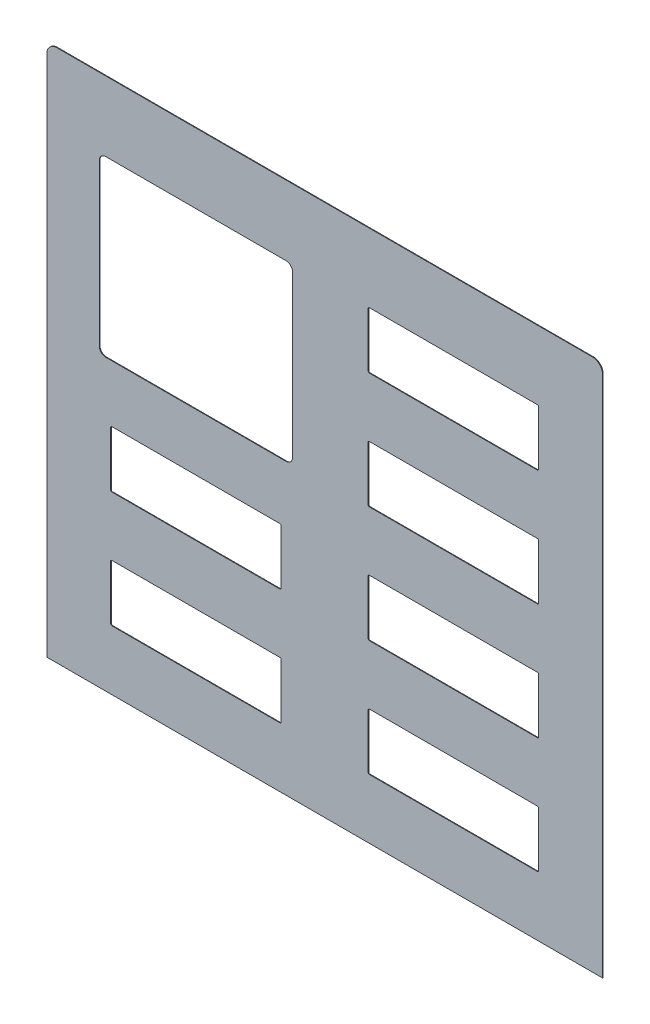
SolidWorks part; units mm, degrees
ref_plane "Front Plane" through (0, 0, 0) normal (0, 0, 1) x (1, 0, 0)
ref_plane "Top Plane" through (0, 0, 0) normal (0, 1, 0) x (1, 0, 0)
ref_plane "Right Plane" through (0, 0, 0) normal (1, 0, 0) x (0, 0, -1)
sketch "Sketch1" plane through (0, 0, 0) normal (0, 0, 1) x (1, 0, 0)
  line L1 (0, 0) -> (863.4, 0)
  line L2 (0, 0) -> (0, 812)
  line L3 (15.7, 827.7) -> (847.7, 827.7)
  line L4 (863.4, 0) -> (863.4, 812)
  arc A0 (847.7, 827.7) -> (863.4, 812) centre (847.7, 812) cw
  arc A1 (0, 812) -> (15.7, 827.7) centre (15.7, 812) cw
  dimension "D3" = 15.7
  dimension "D1" = 863.4
  dimension "D2" = 827.7
base flange "Base-Flange1" sketch "Sketch1" thickness 1 reverse thickness direction no parameters "D1"=1
edge flange "Edge-Flange1" [suppressed] sketch "Sketch8" flange angle 90 flange position material inside bend radius 1 thickness 1
sketch "Sketch8" plane through (0, 0, -1) normal (0, -1, 0) x (-1, 0, 0)
  line L0 (0, 0) -> (-822, 0) construction
  line L1 (-42, 0) -> (-780, 0)
  line L2 (-780, 0) -> (-780, 12)
  line L3 (-780, 12) -> (-42, 12)
  line L4 (-42, 12) -> (-42, 0)
  line L5 (0, 0) -> (0, -1) construction
  line L6 (-822, 0) -> (-822, -1) construction
  circle A0 centre (-81, 6) radius 2.75
  circle A1 centre (-261, 6) radius 2.75
  circle A2 centre (-441, 6) radius 2.75
  circle A3 centre (-621, 6) radius 2.75
  circle A4 centre (-801, 6) radius 2.75
  circle A5 centre (-981, 6) radius 2.75
  circle A6 centre (-1161, 6) radius 2.75
  point P6 (-42, 6)
  dimension "D1" = 5.5
  dimension "D2" = 39
  dimension "D4" = 42
  dimension "D5" = 42
  dimension "D3" = 7
bend "EdgeBend1" bend radius 1 bend angle 90 parameters "D5"=1, "D6"=10, "D7"=12
sketch "Sketch9" plane through (0, 0, 0) normal (0, 0, 1) x (1, 0, 0)
  line L0 (863.4, 0) -> (863.4, 812) construction
  line L1 (762.2, 720.7) -> (501.2, 720.7)
  line L2 (764.2, 718.7) -> (764.2, 634.7)
  line L3 (762.2, 632.7) -> (501.2, 632.7)
  line L4 (499.2, 718.7) -> (499.2, 634.7)
  line L5 (847.7, 827.7) -> (15.7, 827.7) construction
  line L38 (764.2, 538.7) -> (764.2, 454.7)
  line L39 (762.2, 540.7) -> (501.2, 540.7)
  line L40 (762.2, 452.7) -> (501.2, 452.7)
  line L41 (499.2, 538.7) -> (499.2, 454.7)
  line L42 (764.2, 358.7) -> (764.2, 274.7)
  line L43 (762.2, 360.7) -> (501.2, 360.7)
  line L44 (762.2, 272.7) -> (501.2, 272.7)
  line L45 (499.2, 358.7) -> (499.2, 274.7)
  line L46 (764.2, 178.7) -> (764.2, 94.7)
  line L47 (762.2, 180.7) -> (501.2, 180.7)
  line L48 (762.2, 92.7) -> (501.2, 92.7)
  line L49 (499.2, 178.7) -> (499.2, 94.7)
  line L58 (364.2, 358.7) -> (364.2, 274.7)
  line L59 (362.2, 360.7) -> (101.2, 360.7)
  line L60 (362.2, 272.7) -> (101.2, 272.7)
  line L61 (99.2, 358.7) -> (99.2, 274.7)
  line L62 (364.2, 178.7) -> (364.2, 94.7)
  line L63 (362.2, 180.7) -> (101.2, 180.7)
  line L64 (362.2, 92.7) -> (101.2, 92.7)
  line L65 (99.2, 178.7) -> (99.2, 94.7)
  line L66 (364.2, 718.7) -> (364.2, 634.7) [skipped]
  line L67 (362.2, 720.7) -> (101.2, 720.7) [skipped]
  line L68 (362.2, 632.7) -> (101.2, 632.7) [skipped]
  line L69 (99.2, 718.7) -> (99.2, 634.7) [skipped]
  line L70 (364.2, 538.7) -> (364.2, 454.7) [skipped]
  line L71 (362.2, 540.7) -> (101.2, 540.7) [skipped]
  line L72 (362.2, 452.7) -> (101.2, 452.7) [skipped]
  line L73 (99.2, 538.7) -> (99.2, 454.7) [skipped]
  arc A0 (764.2, 634.7) -> (762.2, 632.7) centre (762.2, 634.7) cw
  arc A1 (501.2, 632.7) -> (499.2, 634.7) centre (501.2, 634.7) cw
  arc A2 (501.2, 720.7) -> (499.2, 718.7) centre (501.2, 718.7) ccw
  arc A3 (762.2, 720.7) -> (764.2, 718.7) centre (762.2, 718.7) cw
  arc A36 (762.2, 540.7) -> (764.2, 538.7) centre (762.2, 538.7) cw
  arc A37 (764.2, 454.7) -> (762.2, 452.7) centre (762.2, 454.7) cw
  arc A38 (501.2, 452.7) -> (499.2, 454.7) centre (501.2, 454.7) cw
  arc A39 (501.2, 540.7) -> (499.2, 538.7) centre (501.2, 538.7) ccw
  arc A40 (762.2, 360.7) -> (764.2, 358.7) centre (762.2, 358.7) cw
  arc A41 (764.2, 274.7) -> (762.2, 272.7) centre (762.2, 274.7) cw
  arc A42 (501.2, 272.7) -> (499.2, 274.7) centre (501.2, 274.7) cw
  arc A43 (501.2, 360.7) -> (499.2, 358.7) centre (501.2, 358.7) ccw
  arc A44 (762.2, 180.7) -> (764.2, 178.7) centre (762.2, 178.7) cw
  arc A45 (764.2, 94.7) -> (762.2, 92.7) centre (762.2, 94.7) cw
  arc A46 (501.2, 92.7) -> (499.2, 94.7) centre (501.2, 94.7) cw
  arc A47 (501.2, 180.7) -> (499.2, 178.7) centre (501.2, 178.7) ccw
  arc A56 (362.2, 360.7) -> (364.2, 358.7) centre (362.2, 358.7) cw
  arc A57 (364.2, 274.7) -> (362.2, 272.7) centre (362.2, 274.7) cw
  arc A58 (101.2, 272.7) -> (99.2, 274.7) centre (101.2, 274.7) cw
  arc A59 (101.2, 360.7) -> (99.2, 358.7) centre (101.2, 358.7) ccw
  arc A60 (362.2, 180.7) -> (364.2, 178.7) centre (362.2, 178.7) cw
  arc A61 (364.2, 94.7) -> (362.2, 92.7) centre (362.2, 94.7) cw
  arc A62 (101.2, 92.7) -> (99.2, 94.7) centre (101.2, 94.7) cw
  arc A63 (101.2, 180.7) -> (99.2, 178.7) centre (101.2, 178.7) ccw
  arc A64 (362.2, 720.7) -> (364.2, 718.7) centre (362.2, 718.7) cw [skipped]
  arc A65 (364.2, 634.7) -> (362.2, 632.7) centre (362.2, 634.7) cw [skipped]
  arc A66 (101.2, 632.7) -> (99.2, 634.7) centre (101.2, 634.7) cw [skipped]
  arc A67 (101.2, 720.7) -> (99.2, 718.7) centre (101.2, 718.7) ccw [skipped]
  arc A68 (362.2, 540.7) -> (364.2, 538.7) centre (362.2, 538.7) cw [skipped]
  arc A69 (364.2, 454.7) -> (362.2, 452.7) centre (362.2, 454.7) cw [skipped]
  arc A70 (101.2, 452.7) -> (99.2, 454.7) centre (101.2, 454.7) cw [skipped]
  arc A71 (101.2, 540.7) -> (99.2, 538.7) centre (101.2, 538.7) ccw [skipped]
  dimension "D5" = 2
  dimension "D1" = 99.2
  dimension "D2" = 265
  dimension "D3" = 88
  dimension "D4" = 107
  dimension "D6" = 2
  dimension "D7" = 4
extrude "Cut-Extrude1" cut sketch "Sketch9" against normal blind 10 normal cut yes
sketch "Sketch10" plane through (0, 0, 0) normal (0, 0, 1) x (1, 0, 0)
  line L1 (91.7, 449.2) -> (371.7, 449.2)
  line L2 (81.7, 459.2) -> (81.7, 709.2)
  line L3 (91.7, 719.2) -> (371.7, 719.2)
  line L4 (381.7, 459.2) -> (381.7, 709.2)
  line L6 (863.4, 0) -> (863.4, 812) construction
  line L8 (847.7, 827.7) -> (15.7, 827.7) construction
  arc A0 (91.7, 449.2) -> (81.7, 459.2) centre (91.7, 459.2) cw
  arc A1 (371.7, 449.2) -> (381.7, 459.2) centre (371.7, 459.2) ccw
  arc A2 (81.7, 709.2) -> (91.7, 719.2) centre (91.7, 709.2) cw
  arc A3 (371.7, 719.2) -> (381.7, 709.2) centre (371.7, 709.2) cw
  dimension "D5" = 10
  dimension "D1" = 300
  dimension "D2" = 270
  dimension "D3" = 108.5
  dimension "D4" = 481.7
extrude "Cut-Extrude2" cut sketch "Sketch10" against normal blind 10 normal cut yes
sketch "Bend-Lines1" [suppressed] plane through (0, 0, 0) normal (0, 1, 0) x (1, 0, 0)
sketch "Bounding-Box1" [suppressed] plane through (0, 0, 0) normal (0, 1, 0) x (1, 0, 0)
sheet metal parameters "Sheet-Metal1" thickness 1 parameters "D1"=2
flat pattern "Flat-Pattern1" [suppressed]
sketch "Bend-Lines2" plane through (0, 0, 0) normal (0, 1, 0) x (1, 0, 0)
sketch3d "Bounding-Box2" [suppressed]
  line L0 (15, 15, 0) -> (-1227, 15, 0) construction
  line L1 (15, -935, 0) -> (-1227, -935, 0) construction
  line L2 (15, 15, 0) -> (15, -935, 0) construction
  line L3 (-1227, 15, 0) -> (-1227, -935, 0) construction
sheet metal parameters "Sheet-Metal2" thickness 1 parameters "D1"=2
flat pattern "Flat-Pattern1"
sketch "Bend-Lines2" plane through (0, 0, 0) normal (0, 0, 1) x (1, 0, 0)
  line L0 (0, 0.8219) -> (1242, 0.8219) construction
  line L1 (0, 0.8219) -> (1242, 0.8219) construction
sketch3d "Bounding-Box2" [suppressed]
  line L0 (-15, 15, 0) -> (1227, 15, 0) construction
  line L1 (-15, -946.3562, 0) -> (1227, -946.3562, 0) construction
  line L2 (-15, 15, 0) -> (-15, -946.3562, 0) construction
  line L3 (1227, 15, 0) -> (1227, -946.3562, 0) construction
bend of the flat pattern "Flatten-<EdgeBend1>1"
sheet metal parameters "Sheet-Metal3" thickness 1 parameters "D1"=2
flat pattern "Flat-Pattern1"
sketch "Bend-Lines2" plane through (0, 0, 0) normal (0, 0, 1) x (1, 0, 0)
  line L0 (0, 0.8219) -> (1244, 0.8219) construction
  line L1 (0, 0.8219) -> (1244, 0.8219) construction
sketch3d "Bounding-Box2" [suppressed]
  line L0 (-16, 16, 0) -> (1228, 16, 0) construction
  line L1 (-16, -945.3562, 0) -> (1228, -945.3562, 0) construction
  line L2 (-16, 16, 0) -> (-16, -945.3562, 0) construction
  line L3 (1228, 16, 0) -> (1228, -945.3562, 0) construction
sheet metal parameters "Sheet-Metal4" thickness 1 parameters "D1"=2
flat pattern "Flat-Pattern1"
sketch "Bend-Lines2" plane through (0, 0, 0) normal (0, 0, 1) x (1, 0, 0)
sketch3d "Bounding-Box2" [suppressed]
  line L0 (-15.7, 15.7, 0) -> (847.7, 15.7, 0) construction
  line L1 (-15.7, -812, 0) -> (847.7, -812, 0) construction
  line L2 (-15.7, 15.7, 0) -> (-15.7, -812, 0) construction
  line L3 (847.7, 15.7, 0) -> (847.7, -812, 0) construction
equation "\"D5@Sketch8\"=\"D4@Sketch8\""
